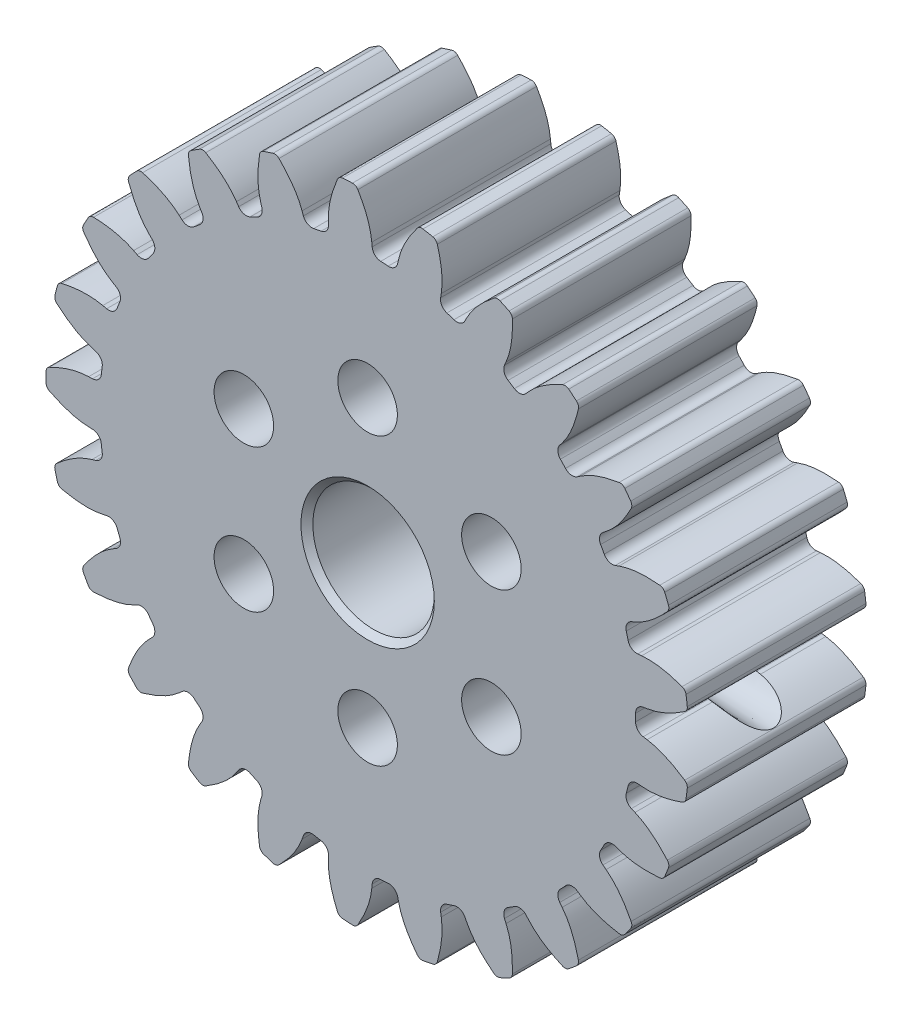
SolidWorks part; units mm, degrees
material "PLA"
ref_plane "前视基准面" through (0, 0, 0) normal (0, 0, 1) x (1, 0, 0)
ref_plane "上视基准面" through (0, 0, 0) normal (0, 1, 0) x (1, 0, 0)
ref_plane "右视基准面" through (0, 0, 0) normal (1, 0, 0) x (0, 0, -1)
sketch "Model" plane through (0, 0, 0) normal (0, 0, 1) x (1, 0, 0)
  line L0 (22.679, 4.7143) -> (23.008, 4.7455)
  line L1 (23.1389, 1.0738) -> (23.4653, 1.1255)
  line L2 (23.1389, -1.0738) -> (23.4653, -1.1255)
  line L3 (22.679, -4.7143) -> (23.008, -4.7455)
  line L4 (22.1449, -6.7945) -> (22.4482, -6.9257)
  line L5 (20.7941, -10.2063) -> (21.105, -10.3182)
  line L6 (19.7595, -12.0883) -> (20.0206, -12.2908)
  line L7 (17.6026, -15.0569) -> (17.876, -15.2427)
  line L8 (16.1325, -16.6225) -> (16.335, -16.8836)
  line L9 (13.3051, -18.9615) -> (13.5236, -19.2094)
  line L10 (11.4918, -20.1122) -> (11.6231, -20.4155)
  line L11 (8.1716, -21.6746) -> (8.3216, -21.9691)
  line L12 (6.1291, -22.3383) -> (6.1808, -22.6647)
  line L13 (2.5246, -23.0258) -> (2.5967, -23.3484)
  line L14 (0.3812, -23.1607) -> (0.3501, -23.4897)
  line L15 (-3.281, -22.9303) -> (-3.2914, -23.2606)
  line L16 (-5.3906, -22.5279) -> (-5.5025, -22.8388)
  line L17 (-8.8804, -21.3939) -> (-8.9727, -21.7113)
  line L18 (-10.8237, -20.4795) -> (-11.0094, -20.7529)
  line L19 (-13.9219, -18.5133) -> (-14.0902, -18.7978)
  line L20 (-15.5767, -17.1444) -> (-15.8246, -17.3629)
  line L21 (-18.0886, -14.4695) -> (-18.3223, -14.7031)
  line L22 (-19.351, -12.732) -> (-19.6454, -12.882)
  line L23 (-21.1187, -9.5164) -> (-21.4032, -9.6846)
  line L24 (-21.9093, -7.5196) -> (-22.2318, -7.5917)
  line L25 (-22.8219, -3.9654) -> (-23.1392, -4.0576)
  line L26 (-23.091, -1.8347) -> (-23.4214, -1.8244)
  line L27 (-23.091, 1.8347) -> (-23.4214, 1.8244)
  line L28 (-22.8219, 3.9654) -> (-23.1392, 4.0576)
  line L29 (-21.9093, 7.5196) -> (-22.2318, 7.5917)
  line L30 (-21.1187, 9.5164) -> (-21.4032, 9.6846)
  line L31 (-19.351, 12.732) -> (-19.6454, 12.882)
  line L32 (-18.0886, 14.4695) -> (-18.3223, 14.7031)
  line L33 (-15.5767, 17.1444) -> (-15.8246, 17.3629)
  line L34 (-13.9219, 18.5133) -> (-14.0902, 18.7978)
  line L35 (-10.8237, 20.4795) -> (-11.0094, 20.7529)
  line L36 (-8.8804, 21.3939) -> (-8.9727, 21.7113)
  line L37 (-5.3906, 22.5279) -> (-5.5025, 22.8388)
  line L38 (-3.281, 22.9303) -> (-3.2914, 23.2606)
  line L39 (0.3812, 23.1607) -> (0.3501, 23.4897)
  line L40 (2.5246, 23.0258) -> (2.5967, 23.3484)
  line L41 (6.1291, 22.3383) -> (6.1808, 22.6647)
  line L42 (8.1716, 21.6746) -> (8.3216, 21.9691)
  line L43 (11.4918, 20.1122) -> (11.6231, 20.4155)
  line L44 (13.3051, 18.9615) -> (13.5236, 19.2094)
  line L45 (16.1325, 16.6225) -> (16.335, 16.8836)
  line L46 (17.6026, 15.0569) -> (17.876, 15.2427)
  line L47 (19.7595, 12.0883) -> (20.0206, 12.2908)
  line L48 (20.7941, 10.2063) -> (21.105, 10.3182)
  line L49 (22.1449, 6.7945) -> (22.4482, 6.9257)
  arc A0 (21.8688, 5.2922) -> (21.7931, 5.5955) centre (0, 0) ccw
  arc A1 (22.5, 0) -> (22.4978, 0.3126) centre (0, 0) ccw
  arc A2 (26.7871, 3.384) -> (26.7311, 3.8011) centre (0, 0) ccw
  arc A3 (26.8366, 2.9661) -> (26.7871, 3.384) centre (0, 0) ccw
  arc A4 (21.8688, 5.2922) -> (22.679, 4.7143) centre (22.6074, 5.4709) ccw
  arc A5 (23.1389, 1.0738) -> (22.4978, 0.3126) centre (23.2578, 0.3232) ccw
  arc A6 (26.7311, 3.8011) -> (26.4032, 4.2019) centre (26.2361, 3.7307) ccw
  arc A7 (26.6187, 2.4963) -> (26.8366, 2.9661) centre (26.3396, 2.9112) ccw
  arc A8 (22.4978, -0.3126) -> (22.5, 0) centre (0, 0) ccw
  arc A9 (21.7931, -5.5955) -> (21.8688, -5.2922) centre (0, 0) ccw
  arc A10 (26.7871, -3.384) -> (26.8366, -2.9661) centre (0, 0) ccw
  arc A11 (26.7311, -3.8011) -> (26.7871, -3.384) centre (0, 0) ccw
  arc A12 (22.4978, -0.3126) -> (23.1389, -1.0738) centre (23.2578, -0.3232) ccw
  arc A13 (22.679, -4.7143) -> (21.8688, -5.2922) centre (22.6074, -5.4709) ccw
  arc A14 (26.8366, -2.9661) -> (26.6187, -2.4963) centre (26.3396, -2.9112) ccw
  arc A15 (26.4032, -4.2019) -> (26.7311, -3.8011) centre (26.2361, -3.7307) ccw
  arc A16 (21.7133, -5.8978) -> (21.7931, -5.5955) centre (0, 0) ccw
  arc A17 (19.7169, -10.8395) -> (19.8656, -10.5645) centre (0, 0) ccw
  arc A18 (25.104, -9.9394) -> (25.2558, -9.5469) centre (0, 0) ccw
  arc A19 (24.946, -10.3294) -> (25.104, -9.9394) centre (0, 0) ccw
  arc A20 (21.7133, -5.8978) -> (22.1449, -6.7945) centre (22.4467, -6.097) ccw
  arc A21 (20.7941, -10.2063) -> (19.8656, -10.5645) centre (20.5366, -10.9213) ccw
  arc A22 (25.2558, -9.5469) -> (25.1616, -9.0377) centre (24.7881, -9.3701) ccw
  arc A23 (24.5287, -10.6361) -> (24.946, -10.3294) centre (24.484, -10.1381) ccw
  arc A24 (19.5644, -11.1124) -> (19.7169, -10.8395) centre (0, 0) ccw
  arc A25 (16.4018, -15.4023) -> (16.6142, -15.1729) centre (0, 0) ccw
  arc A26 (21.8435, -15.8702) -> (22.0881, -15.5278) centre (0, 0) ccw
  arc A27 (21.5935, -16.2087) -> (21.8435, -15.8702) centre (0, 0) ccw
  arc A28 (19.5644, -11.1124) -> (19.7595, -12.0883) centre (20.2252, -11.4877) ccw
  arc A29 (17.6026, -15.0569) -> (16.6142, -15.1729) centre (17.1754, -15.6854) ccw
  arc A30 (22.0881, -15.5278) -> (22.1235, -15.0112) centre (21.6791, -15.2403) ccw
  arc A31 (21.113, -16.402) -> (21.5935, -16.2087) centre (21.1936, -15.9085) ccw
  arc A32 (16.1862, -15.6287) -> (16.4018, -15.4023) centre (0, 0) ccw
  arc A33 (12.0561, -18.9974) -> (12.3189, -18.828) centre (0, 0) ccw
  arc A34 (17.2104, -20.8039) -> (17.5326, -20.5331) centre (0, 0) ccw
  arc A35 (16.8841, -21.0696) -> (17.2104, -20.8039) centre (0, 0) ccw
  arc A36 (16.1862, -15.6287) -> (16.1325, -16.6225) centre (16.7329, -16.1566) ccw
  arc A37 (13.3051, -18.9615) -> (12.3189, -18.828) centre (12.735, -19.464) ccw
  arc A38 (17.5326, -20.5331) -> (17.6953, -20.0415) centre (17.2079, -20.1529) ccw
  arc A39 (16.3707, -21.1373) -> (16.8841, -21.0696) centre (16.5715, -20.6794) ccw
  arc A40 (11.791, -19.1631) -> (12.0561, -18.9974) centre (0, 0) ccw
  arc A41 (6.9529, -21.3988) -> (7.2495, -21.3001) centre (0, 0) ccw
  arc A42 (11.496, -24.4303) -> (11.8754, -24.2482) centre (0, 0) ccw
  arc A43 (11.1139, -24.6065) -> (11.496, -24.4303) centre (0, 0) ccw
  arc A44 (11.791, -19.1631) -> (11.4918, -20.1122) centre (12.1893, -19.8103) ccw
  arc A45 (8.1716, -21.6746) -> (7.2495, -21.3001) centre (7.4944, -22.0196) ccw
  arc A46 (11.8754, -24.2482) -> (12.1553, -23.8125) centre (11.6555, -23.7992) ccw
  arc A47 (10.5997, -24.5445) -> (11.1139, -24.6065) centre (10.9081, -24.1509) ccw
  arc A48 (6.6549, -21.4933) -> (6.9529, -21.3988) centre (0, 0) ccw
  arc A49 (1.4128, -22.4556) -> (1.7246, -22.4338) centre (0, 0) ccw
  arc A50 (5.0593, -26.5218) -> (5.472, -26.4397) centre (0, 0) ccw
  arc A51 (4.6453, -26.5974) -> (5.0593, -26.5218) centre (0, 0) ccw
  arc A52 (6.6549, -21.4933) -> (6.1291, -22.3383) centre (6.8797, -22.2193) ccw
  arc A53 (2.5246, -23.0258) -> (1.7246, -22.4338) centre (1.7829, -23.1916) ccw
  arc A54 (5.472, -26.4397) -> (5.8515, -26.0873) centre (5.3707, -25.9501) ccw
  arc A55 (4.1628, -26.4094) -> (4.6453, -26.5974) centre (4.5593, -26.1048) ccw
  arc A56 (1.1007, -22.4731) -> (1.4128, -22.4556) centre (0, 0) ccw
  arc A57 (-4.2161, -22.1015) -> (-3.9086, -22.1579) centre (0, 0) ccw
  arc A58 (-1.6953, -26.9467) -> (-1.2752, -26.9699) centre (0, 0) ccw
  arc A59 (-2.1151, -26.917) -> (-1.6953, -26.9467) centre (0, 0) ccw
  arc A60 (1.1007, -22.4731) -> (0.3812, -23.1607) centre (1.1378, -23.2322) ccw
  arc A61 (-3.281, -22.9303) -> (-3.9086, -22.1579) centre (-4.0406, -22.9063) ccw
  arc A62 (-1.2752, -26.9699) -> (-0.82, -26.7229) centre (-1.2516, -26.4704) ccw
  arc A63 (-2.5358, -26.6149) -> (-2.1151, -26.917) centre (-2.0759, -26.4186) ccw
  arc A64 (-4.5227, -22.0408) -> (-4.2161, -22.1015) centre (0, 0) ccw
  arc A65 (-9.58, -20.3586) -> (-9.2962, -20.4897) centre (0, 0) ccw
  arc A66 (-8.3435, -25.6785) -> (-7.9422, -25.8054) centre (0, 0) ccw
  arc A67 (-8.7426, -25.5454) -> (-8.3435, -25.6785) centre (0, 0) ccw
  arc A68 (-4.5227, -22.0408) -> (-5.3906, -22.5279) centre (-4.6755, -22.7852) ccw
  arc A69 (-8.8804, -21.3939) -> (-9.2962, -20.4897) centre (-9.6103, -21.1818) ccw
  arc A70 (-7.9422, -25.8054) -> (-7.4399, -25.6794) centre (-7.7952, -25.3276) ccw
  arc A71 (-9.075, -25.1482) -> (-8.7426, -25.5454) centre (-8.5807, -25.0723) ccw
  arc A72 (-9.862, -20.2235) -> (-9.58, -20.3586) centre (0, 0) ccw
  arc A73 (-14.342, -17.3365) -> (-14.0998, -17.5341) centre (0, 0) ccw
  arc A74 (-14.4673, -22.7969) -> (-14.1103, -23.0196) centre (0, 0) ccw
  arc A75 (-14.8209, -22.5686) -> (-14.4673, -22.7969) centre (0, 0) ccw
  arc A76 (-9.862, -20.2235) -> (-10.8237, -20.4795) centre (-10.1951, -20.9066) ccw
  arc A77 (-13.9219, -18.5133) -> (-14.0998, -17.5341) centre (-14.576, -18.1264) ccw
  arc A78 (-14.1103, -23.0196) -> (-13.5924, -23.0224) centre (-13.849, -22.5933) ccw
  arc A79 (-15.0439, -22.1012) -> (-14.8209, -22.5686) centre (-14.5464, -22.1507) ccw
  arc A80 (-14.5815, -17.1356) -> (-14.342, -17.3365) centre (0, 0) ccw
  arc A81 (-18.2029, -13.2252) -> (-18.0174, -13.4768) centre (0, 0) ccw
  arc A82 (-19.6822, -18.4828) -> (-19.3917, -18.7873) centre (0, 0) ccw
  arc A83 (-19.9678, -18.1738) -> (-19.6822, -18.4828) centre (0, 0) ccw
  arc A84 (-14.5815, -17.1356) -> (-15.5767, -17.1444) centre (-15.0741, -17.7144) ccw
  arc A85 (-18.0886, -14.4695) -> (-18.0174, -13.4768) centre (-18.626, -13.932) ccw
  arc A86 (-19.3917, -18.7873) -> (-18.8908, -18.9188) centre (-19.0326, -18.4394) ccw
  arc A87 (-20.0677, -17.6656) -> (-19.9678, -18.1738) centre (-19.598, -17.8372) ccw
  arc A88 (-18.3849, -12.971) -> (-18.2029, -13.2252) centre (0, 0) ccw
  arc A89 (-20.92, -8.2828) -> (-20.8029, -8.5727) centre (0, 0) ccw
  arc A90 (-23.6603, -13.0073) -> (-23.4547, -13.3745) centre (0, 0) ccw
  arc A91 (-23.8601, -12.637) -> (-23.6603, -13.0073) centre (0, 0) ccw
  arc A92 (-18.3849, -12.971) -> (-19.351, -12.732) centre (-19.0059, -13.4091) ccw
  arc A93 (-21.1187, -9.5164) -> (-20.8029, -8.5727) centre (-21.5055, -8.8622) ccw
  arc A94 (-23.4547, -13.3745) -> (-23.0022, -13.6265) centre (-23.0203, -13.1268) ccw
  arc A95 (-23.8305, -12.12) -> (-23.8601, -12.637) centre (-23.4183, -12.403) ccw
  arc A96 (-21.033, -7.9913) -> (-20.92, -8.2828) centre (0, 0) ccw
  arc A97 (-22.3226, -2.82) -> (-22.2812, -3.1299) centre (0, 0) ccw
  arc A98 (-26.1517, -6.7146) -> (-26.0439, -7.1214) centre (0, 0) ccw
  arc A99 (-26.2532, -6.3062) -> (-26.1517, -6.7146) centre (0, 0) ccw
  arc A100 (-21.033, -7.9913) -> (-21.9093, -7.5196) centre (-21.7435, -8.2613) ccw
  arc A101 (-22.8219, -3.9654) -> (-22.2812, -3.1299) centre (-23.0339, -3.2356) ccw
  arc A102 (-26.0439, -7.1214) -> (-25.6684, -7.478) centre (-25.5616, -6.9895) ccw
  arc A103 (-26.0959, -5.8128) -> (-26.2532, -6.3062) centre (-25.767, -6.1895) ccw
  arc A104 (-22.3596, -2.5096) -> (-22.3226, -2.82) centre (0, 0) ccw
  arc A105 (-22.3226, 2.82) -> (-22.3596, 2.5096) centre (0, 0) ccw
  arc A106 (-27, 0) -> (-26.9967, -0.4208) centre (0, 0) ccw
  arc A107 (-26.9967, 0.4208) -> (-27, 0) centre (0, 0) ccw
  arc A108 (-22.3596, -2.5096) -> (-23.091, -1.8347) centre (-23.1149, -2.5943) ccw
  arc A109 (-23.091, 1.8347) -> (-22.3596, 2.5096) centre (-23.1149, 2.5943) ccw
  arc A110 (-26.9967, -0.4208) -> (-26.7216, -0.8596) centre (-26.4968, -0.413) ccw
  arc A111 (-26.7216, 0.8596) -> (-26.9967, 0.4208) centre (-26.4968, 0.413) ccw
  arc A112 (-22.2812, 3.1299) -> (-22.3226, 2.82) centre (0, 0) ccw
  arc A113 (-20.92, 8.2828) -> (-21.033, 7.9913) centre (0, 0) ccw
  arc A114 (-26.1517, 6.7146) -> (-26.2532, 6.3062) centre (0, 0) ccw
  arc A115 (-26.0439, 7.1214) -> (-26.1517, 6.7146) centre (0, 0) ccw
  arc A116 (-22.2812, 3.1299) -> (-22.8219, 3.9654) centre (-23.0339, 3.2356) ccw
  arc A117 (-21.9093, 7.5196) -> (-21.033, 7.9913) centre (-21.7435, 8.2613) ccw
  arc A118 (-26.2532, 6.3062) -> (-26.0959, 5.8128) centre (-25.767, 6.1895) ccw
  arc A119 (-25.6684, 7.478) -> (-26.0439, 7.1214) centre (-25.5616, 6.9895) ccw
  arc A120 (-20.8029, 8.5727) -> (-20.92, 8.2828) centre (0, 0) ccw
  arc A121 (-18.2029, 13.2252) -> (-18.3849, 12.971) centre (0, 0) ccw
  arc A122 (-23.6603, 13.0073) -> (-23.8601, 12.637) centre (0, 0) ccw
  arc A123 (-23.4547, 13.3745) -> (-23.6603, 13.0073) centre (0, 0) ccw
  arc A124 (-20.8029, 8.5727) -> (-21.1187, 9.5164) centre (-21.5055, 8.8622) ccw
  arc A125 (-19.351, 12.732) -> (-18.3849, 12.971) centre (-19.0059, 13.4091) ccw
  arc A126 (-23.8601, 12.637) -> (-23.8305, 12.12) centre (-23.4183, 12.403) ccw
  arc A127 (-23.0022, 13.6265) -> (-23.4547, 13.3745) centre (-23.0203, 13.1268) ccw
  arc A128 (-18.0174, 13.4768) -> (-18.2029, 13.2252) centre (0, 0) ccw
  arc A129 (-14.342, 17.3365) -> (-14.5815, 17.1356) centre (0, 0) ccw
  arc A130 (-19.6822, 18.4828) -> (-19.9678, 18.1738) centre (0, 0) ccw
  arc A131 (-19.3917, 18.7873) -> (-19.6822, 18.4828) centre (0, 0) ccw
  arc A132 (-18.0174, 13.4768) -> (-18.0886, 14.4695) centre (-18.626, 13.932) ccw
  arc A133 (-15.5767, 17.1444) -> (-14.5815, 17.1356) centre (-15.0741, 17.7144) ccw
  arc A134 (-19.9678, 18.1738) -> (-20.0677, 17.6656) centre (-19.598, 17.8372) ccw
  arc A135 (-18.8908, 18.9188) -> (-19.3917, 18.7873) centre (-19.0326, 18.4394) ccw
  arc A136 (-14.0998, 17.5341) -> (-14.342, 17.3365) centre (0, 0) ccw
  arc A137 (-9.58, 20.3586) -> (-9.862, 20.2235) centre (0, 0) ccw
  arc A138 (-14.4673, 22.7969) -> (-14.8209, 22.5686) centre (0, 0) ccw
  arc A139 (-14.1103, 23.0196) -> (-14.4673, 22.7969) centre (0, 0) ccw
  arc A140 (-14.0998, 17.5341) -> (-13.9219, 18.5133) centre (-14.576, 18.1264) ccw
  arc A141 (-10.8237, 20.4795) -> (-9.862, 20.2235) centre (-10.1951, 20.9066) ccw
  arc A142 (-14.8209, 22.5686) -> (-15.0439, 22.1012) centre (-14.5464, 22.1507) ccw
  arc A143 (-13.5924, 23.0224) -> (-14.1103, 23.0196) centre (-13.849, 22.5933) ccw
  arc A144 (-9.2962, 20.4897) -> (-9.58, 20.3586) centre (0, 0) ccw
  arc A145 (-4.2161, 22.1015) -> (-4.5228, 22.0408) centre (0, 0) ccw
  arc A146 (-8.3435, 25.6785) -> (-8.7426, 25.5454) centre (0, 0) ccw
  arc A147 (-7.9422, 25.8054) -> (-8.3435, 25.6785) centre (0, 0) ccw
  arc A148 (-9.2962, 20.4897) -> (-8.8804, 21.3939) centre (-9.6103, 21.1818) ccw
  arc A149 (-5.3906, 22.5279) -> (-4.5228, 22.0408) centre (-4.6755, 22.7852) ccw
  arc A150 (-8.7426, 25.5454) -> (-9.075, 25.1482) centre (-8.5807, 25.0723) ccw
  arc A151 (-7.4399, 25.6794) -> (-7.9422, 25.8054) centre (-7.7952, 25.3276) ccw
  arc A152 (-3.9086, 22.1579) -> (-4.2161, 22.1015) centre (0, 0) ccw
  arc A153 (1.4128, 22.4556) -> (1.1007, 22.4731) centre (0, 0) ccw
  arc A154 (-1.6953, 26.9467) -> (-2.1151, 26.917) centre (0, 0) ccw
  arc A155 (-1.2752, 26.9699) -> (-1.6953, 26.9467) centre (0, 0) ccw
  arc A156 (-3.9086, 22.1579) -> (-3.281, 22.9303) centre (-4.0406, 22.9063) ccw
  arc A157 (0.3812, 23.1607) -> (1.1007, 22.4731) centre (1.1378, 23.2322) ccw
  arc A158 (-2.1151, 26.917) -> (-2.5358, 26.6149) centre (-2.0759, 26.4186) ccw
  arc A159 (-0.82, 26.7229) -> (-1.2752, 26.9699) centre (-1.2516, 26.4704) ccw
  arc A160 (1.7246, 22.4338) -> (1.4128, 22.4556) centre (0, 0) ccw
  arc A161 (6.9529, 21.3988) -> (6.6549, 21.4933) centre (0, 0) ccw
  arc A162 (5.0593, 26.5218) -> (4.6453, 26.5974) centre (0, 0) ccw
  arc A163 (5.472, 26.4397) -> (5.0593, 26.5218) centre (0, 0) ccw
  arc A164 (1.7246, 22.4338) -> (2.5246, 23.0258) centre (1.7829, 23.1916) ccw
  arc A165 (6.1291, 22.3383) -> (6.6549, 21.4933) centre (6.8797, 22.2193) ccw
  arc A166 (4.6453, 26.5974) -> (4.1628, 26.4094) centre (4.5593, 26.1048) ccw
  arc A167 (5.8515, 26.0873) -> (5.472, 26.4397) centre (5.3707, 25.9501) ccw
  arc A168 (7.2495, 21.3001) -> (6.9529, 21.3988) centre (0, 0) ccw
  arc A169 (12.0561, 18.9974) -> (11.791, 19.1631) centre (0, 0) ccw
  arc A170 (11.496, 24.4303) -> (11.1139, 24.6065) centre (0, 0) ccw
  arc A171 (11.8754, 24.2482) -> (11.496, 24.4303) centre (0, 0) ccw
  arc A172 (7.2495, 21.3001) -> (8.1716, 21.6746) centre (7.4944, 22.0196) ccw
  arc A173 (11.4918, 20.1122) -> (11.791, 19.1631) centre (12.1893, 19.8103) ccw
  arc A174 (11.1139, 24.6065) -> (10.5997, 24.5445) centre (10.9081, 24.1509) ccw
  arc A175 (12.1553, 23.8125) -> (11.8754, 24.2482) centre (11.6555, 23.7992) ccw
  arc A176 (12.3189, 18.828) -> (12.0561, 18.9974) centre (0, 0) ccw
  arc A177 (16.4018, 15.4023) -> (16.1862, 15.6287) centre (0, 0) ccw
  arc A178 (17.2104, 20.8039) -> (16.8841, 21.0696) centre (0, 0) ccw
  arc A179 (17.5326, 20.5331) -> (17.2104, 20.8039) centre (0, 0) ccw
  arc A180 (12.3189, 18.828) -> (13.3051, 18.9615) centre (12.735, 19.464) ccw
  arc A181 (16.1325, 16.6225) -> (16.1862, 15.6287) centre (16.7329, 16.1566) ccw
  arc A182 (16.8841, 21.0696) -> (16.3707, 21.1373) centre (16.5715, 20.6794) ccw
  arc A183 (17.6953, 20.0415) -> (17.5326, 20.5331) centre (17.2079, 20.1529) ccw
  arc A184 (16.6142, 15.1729) -> (16.4018, 15.4023) centre (0, 0) ccw
  arc A185 (19.7169, 10.8395) -> (19.5644, 11.1124) centre (0, 0) ccw
  arc A186 (21.8435, 15.8702) -> (21.5935, 16.2087) centre (0, 0) ccw
  arc A187 (22.0881, 15.5278) -> (21.8435, 15.8702) centre (0, 0) ccw
  arc A188 (16.6142, 15.1729) -> (17.6026, 15.0569) centre (17.1754, 15.6854) ccw
  arc A189 (19.7595, 12.0883) -> (19.5644, 11.1124) centre (20.2252, 11.4877) ccw
  arc A190 (21.5935, 16.2087) -> (21.113, 16.402) centre (21.1936, 15.9085) ccw
  arc A191 (22.1235, 15.0112) -> (22.0881, 15.5278) centre (21.6791, 15.2403) ccw
  arc A192 (19.8656, 10.5645) -> (19.7169, 10.8395) centre (0, 0) ccw
  arc A193 (21.7931, 5.5955) -> (21.7133, 5.8978) centre (0, 0) ccw
  arc A194 (25.104, 9.9394) -> (24.946, 10.3294) centre (0, 0) ccw
  arc A195 (25.2558, 9.5469) -> (25.104, 9.9394) centre (0, 0) ccw
  arc A196 (19.8656, 10.5645) -> (20.7941, 10.2063) centre (20.5366, 10.9213) ccw
  arc A197 (22.1449, 6.7945) -> (21.7133, 5.8978) centre (22.4467, 6.097) ccw
  arc A198 (24.946, 10.3294) -> (24.5287, 10.6361) centre (24.484, 10.1381) ccw
  arc A199 (25.1616, 9.0377) -> (25.2558, 9.5469) centre (24.7881, 9.3701) ccw
  spline S0 degree 3 poles (23.008, 4.7455) (23.3027, 4.7733) (23.9094, 4.7799) (24.8282, 4.659) (25.6628, 4.4508) (26.1863, 4.2788) (26.4032, 4.2019) knots 0 0 0 0 0.887831 1.811653 2.773452 3.463896 3.463896 3.463896 3.463896
  spline S1 degree 3 poles (23.4653, 1.1255) (23.7576, 1.1718) (24.3469, 1.3163) (25.2069, 1.6619) (25.9634, 2.0711) (26.4277, 2.3679) (26.6187, 2.4963) knots 0 0 0 0 0.887831 1.811653 2.773452 3.463896 3.463896 3.463896 3.463896
  spline S2 degree 3 poles (23.4653, -1.1255) (23.7576, -1.1718) (24.3469, -1.3163) (25.2069, -1.6619) (25.9634, -2.0711) (26.4277, -2.3679) (26.6187, -2.4963) knots 0 0 0 0 0.887831 1.811653 2.773452 3.463896 3.463896 3.463896 3.463896
  spline S3 degree 3 poles (23.008, -4.7455) (23.3027, -4.7733) (23.9094, -4.7799) (24.8282, -4.659) (25.6628, -4.4508) (26.1863, -4.2788) (26.4032, -4.2019) knots 0 0 0 0 0.887831 1.811653 2.773452 3.463896 3.463896 3.463896 3.463896
  spline S4 degree 3 poles (22.4482, -6.9257) (22.7198, -7.0432) (23.2547, -7.3298) (24.0017, -7.8784) (24.6327, -8.4629) (25.0086, -8.8658) (25.1616, -9.0377) knots 0 0 0 0 0.887831 1.811653 2.773452 3.463896 3.463896 3.463896 3.463896
  spline S5 degree 3 poles (21.105, -10.3182) (21.3835, -10.4185) (21.9695, -10.5758) (22.8896, -10.6872) (23.7497, -10.693) (24.2995, -10.6567) (24.5287, -10.6361) knots 0 0 0 0 0.887831 1.811653 2.773452 3.463896 3.463896 3.463896 3.463896
  spline S6 degree 3 poles (20.0206, -12.2908) (20.2545, -12.4722) (20.7013, -12.8827) (21.2883, -13.5998) (21.7542, -14.3229) (22.018, -14.8066) (22.1235, -15.0112) knots 0 0 0 0 0.887831 1.811653 2.773452 3.463896 3.463896 3.463896 3.463896
  spline S7 degree 3 poles (17.876, -15.2427) (18.1207, -15.409) (18.6492, -15.7071) (19.5127, -16.0438) (20.3443, -16.2634) (20.8859, -16.3649) (21.113, -16.402) knots 0 0 0 0 0.887831 1.811653 2.773452 3.463896 3.463896 3.463896 3.463896
  spline S8 degree 3 poles (16.335, -16.8836) (16.5164, -17.1174) (16.8471, -17.6261) (17.2374, -18.4667) (17.5088, -19.283) (17.6441, -19.8171) (17.6953, -20.0415) knots 0 0 0 0 0.887831 1.811653 2.773452 3.463896 3.463896 3.463896 3.463896
  spline S9 degree 3 poles (13.5236, -19.2094) (13.7193, -19.4314) (14.1571, -19.8515) (14.9097, -20.3924) (15.6606, -20.8119) (16.1599, -21.0449) (16.3707, -21.1373) knots 0 0 0 0 0.887831 1.811653 2.773452 3.463896 3.463896 3.463896 3.463896
  spline S10 degree 3 poles (11.6231, -20.4155) (11.7406, -20.6871) (11.9344, -21.2621) (12.1033, -22.1733) (12.1632, -23.0314) (12.1614, -23.5824) (12.1553, -23.8125) knots 0 0 0 0 0.887831 1.811653 2.773452 3.463896 3.463896 3.463896 3.463896
  spline S11 degree 3 poles (8.3216, -21.9691) (8.4559, -22.2328) (8.7755, -22.7485) (9.3699, -23.4596) (9.9929, -24.0527) (10.4186, -24.4025) (10.5997, -24.5445) knots 0 0 0 0 0.887831 1.811653 2.773452 3.463896 3.463896 3.463896 3.463896
  spline S12 degree 3 poles (6.1808, -22.6647) (6.2271, -22.957) (6.2718, -23.5621) (6.2088, -24.4867) (6.0534, -25.3327) (5.9146, -25.8659) (5.8515, -26.0873) knots 0 0 0 0 0.887831 1.811653 2.773452 3.463896 3.463896 3.463896 3.463896
  spline S13 degree 3 poles (2.5967, -23.3484) (2.6612, -23.6372) (2.8424, -24.2162) (3.2414, -25.0528) (3.6973, -25.7822) (4.0226, -26.2269) (4.1628, -26.4094) knots 0 0 0 0 0.887831 1.811653 2.773452 3.463896 3.463896 3.463896 3.463896
  spline S14 degree 3 poles (0.3501, -23.4897) (0.3223, -23.7843) (0.2151, -24.3815) (-0.0758, -25.2615) (-0.4368, -26.0423) (-0.7038, -26.5242) (-0.82, -26.7229) knots 0 0 0 0 0.887831 1.811653 2.773452 3.463896 3.463896 3.463896 3.463896
  spline S15 degree 3 poles (-3.2914, -23.2606) (-3.3007, -23.5564) (-3.2692, -24.1623) (-3.0909, -25.0718) (-2.8306, -25.8917) (-2.6261, -26.4033) (-2.5358, -26.6149) knots 0 0 0 0 0.887831 1.811653 2.773452 3.463896 3.463896 3.463896 3.463896
  spline S16 degree 3 poles (-5.5025, -22.8388) (-5.6028, -23.1173) (-5.8551, -23.669) (-6.3557, -24.449) (-6.8995, -25.1155) (-7.278, -25.5159) (-7.4399, -25.6794) knots 0 0 0 0 0.887831 1.811653 2.773452 3.463896 3.463896 3.463896 3.463896
  spline S17 degree 3 poles (-8.9727, -21.7113) (-9.0553, -21.9955) (-9.1754, -22.5902) (-9.2289, -23.5155) (-9.1807, -24.3743) (-9.1099, -24.9207) (-9.075, -25.1482) knots 0 0 0 0 0.887831 1.811653 2.773452 3.463896 3.463896 3.463896 3.463896
  spline S18 degree 3 poles (-11.0094, -20.7529) (-11.1758, -20.9976) (-11.5574, -21.4693) (-12.2363, -22.1003) (-12.9287, -22.6106) (-13.3949, -22.9043) (-13.5924, -23.0224) knots 0 0 0 0 0.887831 1.811653 2.773452 3.463896 3.463896 3.463896 3.463896
  spline S19 degree 3 poles (-14.0902, -18.7978) (-14.2408, -19.0525) (-14.5051, -19.5987) (-14.787, -20.4815) (-14.9539, -21.3254) (-15.0212, -21.8722) (-15.0439, -22.1012) knots 0 0 0 0 0.887831 1.811653 2.773452 3.463896 3.463896 3.463896 3.463896
  spline S20 degree 3 poles (-15.8246, -17.3629) (-16.0466, -17.5587) (-16.5335, -17.9206) (-17.348, -18.3629) (-18.1456, -18.685) (-18.6701, -18.8536) (-18.8908, -18.9188) knots 0 0 0 0 0.887831 1.811653 2.773452 3.463896 3.463896 3.463896 3.463896
  spline S21 degree 3 poles (-18.3223, -14.7031) (-18.5316, -14.9124) (-18.9234, -15.3757) (-19.416, -16.1607) (-19.7875, -16.9365) (-19.9887, -17.4494) (-20.0677, -17.6656) knots 0 0 0 0 0.887831 1.811653 2.773452 3.463896 3.463896 3.463896 3.463896
  spline S22 degree 3 poles (-19.6454, -12.882) (-19.9091, -13.0164) (-20.4708, -13.2459) (-21.3696, -13.4717) (-22.2222, -13.5854) (-22.7722, -13.6182) (-23.0022, -13.6265) knots 0 0 0 0 0.887831 1.811653 2.773452 3.463896 3.463896 3.463896 3.463896
  spline S23 degree 3 poles (-21.4032, -9.6846) (-21.6579, -9.8353) (-22.1526, -10.1865) (-22.825, -10.8244) (-23.3778, -11.4835) (-23.7002, -11.9303) (-23.8305, -12.12) knots 0 0 0 0 0.887831 1.811653 2.773452 3.463896 3.463896 3.463896 3.463896
  spline S24 degree 3 poles (-22.2318, -7.5917) (-22.5207, -7.6563) (-23.1218, -7.7389) (-24.0485, -7.7341) (-24.9026, -7.6321) (-25.4435, -7.5271) (-25.6684, -7.478) knots 0 0 0 0 0.887831 1.811653 2.773452 3.463896 3.463896 3.463896 3.463896
  spline S25 degree 3 poles (-23.1392, -4.0576) (-23.4234, -4.1402) (-23.99, -4.3574) (-24.7998, -4.808) (-25.4991, -5.3089) (-25.9225, -5.6615) (-26.0959, -5.8128) knots 0 0 0 0 0.887831 1.811653 2.773452 3.463896 3.463896 3.463896 3.463896
  spline S26 degree 3 poles (-23.4214, -1.8244) (-23.7172, -1.8151) (-24.3199, -1.7456) (-25.2164, -1.5105) (-26.0183, -1.1993) (-26.5161, -0.9631) (-26.7216, -0.8596) knots 0 0 0 0 0.887831 1.811653 2.773452 3.463896 3.463896 3.463896 3.463896
  spline S27 degree 3 poles (-23.4214, 1.8244) (-23.7172, 1.8151) (-24.3199, 1.7456) (-25.2164, 1.5105) (-26.0183, 1.1993) (-26.5161, 0.9631) (-26.7216, 0.8596) knots 0 0 0 0 0.887831 1.811653 2.773452 3.463896 3.463896 3.463896 3.463896
  spline S28 degree 3 poles (-23.1392, 4.0576) (-23.4234, 4.1402) (-23.99, 4.3574) (-24.7998, 4.808) (-25.4991, 5.3089) (-25.9225, 5.6615) (-26.0959, 5.8128) knots 0 0 0 0 0.887831 1.811653 2.773452 3.463896 3.463896 3.463896 3.463896
  spline S29 degree 3 poles (-22.2318, 7.5917) (-22.5207, 7.6563) (-23.1218, 7.7389) (-24.0485, 7.7341) (-24.9026, 7.6321) (-25.4435, 7.5271) (-25.6684, 7.478) knots 0 0 0 0 0.887831 1.811653 2.773452 3.463896 3.463896 3.463896 3.463896
  spline S30 degree 3 poles (-21.4032, 9.6846) (-21.6579, 9.8353) (-22.1526, 10.1865) (-22.825, 10.8244) (-23.3778, 11.4835) (-23.7002, 11.9303) (-23.8305, 12.12) knots 0 0 0 0 0.887831 1.811653 2.773452 3.463896 3.463896 3.463896 3.463896
  spline S31 degree 3 poles (-19.6454, 12.882) (-19.9091, 13.0164) (-20.4708, 13.2459) (-21.3696, 13.4717) (-22.2222, 13.5854) (-22.7722, 13.6182) (-23.0022, 13.6265) knots 0 0 0 0 0.887831 1.811653 2.773452 3.463896 3.463896 3.463896 3.463896
  spline S32 degree 3 poles (-18.3223, 14.7031) (-18.5316, 14.9124) (-18.9234, 15.3757) (-19.416, 16.1607) (-19.7875, 16.9365) (-19.9887, 17.4494) (-20.0677, 17.6656) knots 0 0 0 0 0.887831 1.811653 2.773452 3.463896 3.463896 3.463896 3.463896
  spline S33 degree 3 poles (-15.8246, 17.3629) (-16.0466, 17.5587) (-16.5335, 17.9206) (-17.348, 18.3629) (-18.1456, 18.685) (-18.6701, 18.8536) (-18.8908, 18.9188) knots 0 0 0 0 0.887831 1.811653 2.773452 3.463896 3.463896 3.463896 3.463896
  spline S34 degree 3 poles (-14.0902, 18.7978) (-14.2408, 19.0525) (-14.5051, 19.5987) (-14.787, 20.4815) (-14.9539, 21.3254) (-15.0212, 21.8722) (-15.0439, 22.1012) knots 0 0 0 0 0.887831 1.811653 2.773452 3.463896 3.463896 3.463896 3.463896
  spline S35 degree 3 poles (-11.0094, 20.7529) (-11.1758, 20.9976) (-11.5574, 21.4693) (-12.2363, 22.1003) (-12.9287, 22.6106) (-13.3949, 22.9043) (-13.5924, 23.0224) knots 0 0 0 0 0.887831 1.811653 2.773452 3.463896 3.463896 3.463896 3.463896
  spline S36 degree 3 poles (-8.9727, 21.7113) (-9.0553, 21.9955) (-9.1754, 22.5902) (-9.2289, 23.5155) (-9.1807, 24.3743) (-9.1099, 24.9207) (-9.075, 25.1482) knots 0 0 0 0 0.887831 1.811653 2.773452 3.463896 3.463896 3.463896 3.463896
  spline S37 degree 3 poles (-5.5025, 22.8388) (-5.6028, 23.1173) (-5.8551, 23.669) (-6.3557, 24.449) (-6.8995, 25.1155) (-7.278, 25.5159) (-7.4399, 25.6794) knots 0 0 0 0 0.887831 1.811653 2.773452 3.463896 3.463896 3.463896 3.463896
  spline S38 degree 3 poles (-3.2914, 23.2606) (-3.3007, 23.5564) (-3.2692, 24.1623) (-3.0909, 25.0718) (-2.8306, 25.8917) (-2.6261, 26.4033) (-2.5358, 26.6149) knots 0 0 0 0 0.887831 1.811653 2.773452 3.463896 3.463896 3.463896 3.463896
  spline S39 degree 3 poles (0.3501, 23.4897) (0.3223, 23.7843) (0.2151, 24.3815) (-0.0758, 25.2615) (-0.4368, 26.0423) (-0.7038, 26.5242) (-0.82, 26.7229) knots 0 0 0 0 0.887831 1.811653 2.773452 3.463896 3.463896 3.463896 3.463896
  spline S40 degree 3 poles (2.5967, 23.3484) (2.6612, 23.6372) (2.8424, 24.2162) (3.2414, 25.0528) (3.6973, 25.7822) (4.0226, 26.2269) (4.1628, 26.4094) knots 0 0 0 0 0.887831 1.811653 2.773452 3.463896 3.463896 3.463896 3.463896
  spline S41 degree 3 poles (6.1808, 22.6647) (6.2271, 22.957) (6.2718, 23.5621) (6.2088, 24.4867) (6.0534, 25.3327) (5.9146, 25.8659) (5.8515, 26.0873) knots 0 0 0 0 0.887831 1.811653 2.773452 3.463896 3.463896 3.463896 3.463896
  spline S42 degree 3 poles (8.3216, 21.9691) (8.4559, 22.2328) (8.7755, 22.7485) (9.3699, 23.4596) (9.9929, 24.0527) (10.4186, 24.4025) (10.5997, 24.5445) knots 0 0 0 0 0.887831 1.811653 2.773452 3.463896 3.463896 3.463896 3.463896
  spline S43 degree 3 poles (11.6231, 20.4155) (11.7406, 20.6871) (11.9344, 21.2621) (12.1033, 22.1733) (12.1632, 23.0314) (12.1614, 23.5824) (12.1553, 23.8125) knots 0 0 0 0 0.887831 1.811653 2.773452 3.463896 3.463896 3.463896 3.463896
  spline S44 degree 3 poles (13.5236, 19.2094) (13.7193, 19.4314) (14.1571, 19.8515) (14.9097, 20.3924) (15.6606, 20.8119) (16.1599, 21.0449) (16.3707, 21.1373) knots 0 0 0 0 0.887831 1.811653 2.773452 3.463896 3.463896 3.463896 3.463896
  spline S45 degree 3 poles (16.335, 16.8836) (16.5164, 17.1174) (16.8471, 17.6261) (17.2374, 18.4667) (17.5088, 19.283) (17.6441, 19.8171) (17.6953, 20.0415) knots 0 0 0 0 0.887831 1.811653 2.773452 3.463896 3.463896 3.463896 3.463896
  spline S46 degree 3 poles (17.876, 15.2427) (18.1207, 15.409) (18.6492, 15.7071) (19.5127, 16.0438) (20.3443, 16.2634) (20.8859, 16.3649) (21.113, 16.402) knots 0 0 0 0 0.887831 1.811653 2.773452 3.463896 3.463896 3.463896 3.463896
  spline S47 degree 3 poles (20.0206, 12.2908) (20.2545, 12.4722) (20.7013, 12.8827) (21.2883, 13.5998) (21.7542, 14.3229) (22.018, 14.8066) (22.1235, 15.0112) knots 0 0 0 0 0.887831 1.811653 2.773452 3.463896 3.463896 3.463896 3.463896
  spline S48 degree 3 poles (21.105, 10.3182) (21.3835, 10.4185) (21.9695, 10.5758) (22.8896, 10.6872) (23.7497, 10.693) (24.2995, 10.6567) (24.5287, 10.6361) knots 0 0 0 0 0.887831 1.811653 2.773452 3.463896 3.463896 3.463896 3.463896
  spline S49 degree 3 poles (22.4482, 6.9257) (22.7198, 7.0432) (23.2547, 7.3298) (24.0017, 7.8784) (24.6327, 8.4629) (25.0086, 8.8658) (25.1616, 9.0377) knots 0 0 0 0 0.887831 1.811653 2.773452 3.463896 3.463896 3.463896 3.463896
  point P429 (0, 0)
  dimension "D1" = 25
extrude "凸台-拉伸1" add sketch "Model" along normal blind 15
sketch "草图2" plane through (0, 0, 15) normal (0, 0, 1) x (1, 0, 0)
  circle A0 centre (0, 0) radius 5.1
  dimension "D1" = 10.2
extrude "切除-拉伸1" cut sketch "草图2" against normal through all
sketch "草图3" plane through (0, 0, 0) normal (1, 0, 0) x (0, 0, -1)
  line L0 (0, 0) -> (-15, 0) construction
  line L1 (-15, 0.3126) -> (-15, -0.3126) construction
  circle A0 centre (-7.5, 0) radius 1.4
  dimension "D1" = 2.8
extrude "切除-拉伸2" cut sketch "草图3" along normal through all and the other way blind 10
ref_plane "基准面1" through (10, 0, 0) normal (1, 0, 0) x (0, 0, -1)
sketch "草图4" plane through (10, 0, 0) normal (1, 0, 0) x (0, 0, -1)
  circle A0 centre (-7.5, 0) radius 1.6
  dimension "D1" = 3.2
extrude "切除-拉伸3" cut sketch "草图4" along normal through all draft 3 draft outward yes
chamfer "倒角1" distance 0.5 angle 45 2 edges at (5.1, 0, 0) (5.1, 0, 15)
sketch "草图5" plane through (0, 0, 15) normal (0, 0, 1) x (1, 0, 0)
  circle A0 centre (0, 12) radius 2.5
  circle A1 centre (10.3923, 6) radius 2.5
  circle A2 centre (10.3923, -6) radius 2.5
  circle A3 centre (0, -12) radius 2.5
  circle A4 centre (-10.3923, -6) radius 2.5
  circle A5 centre (-10.3923, 6) radius 2.5
  point P4 (-16.5322, -6.6315)
  point P5 (0, 0)
  point P15 (0, 0)
  dimension "D1" = 12
  dimension "D2" = 5
  dimension "D3" = 6
extrude "切除-拉伸4" cut sketch "草图5" against normal through all
